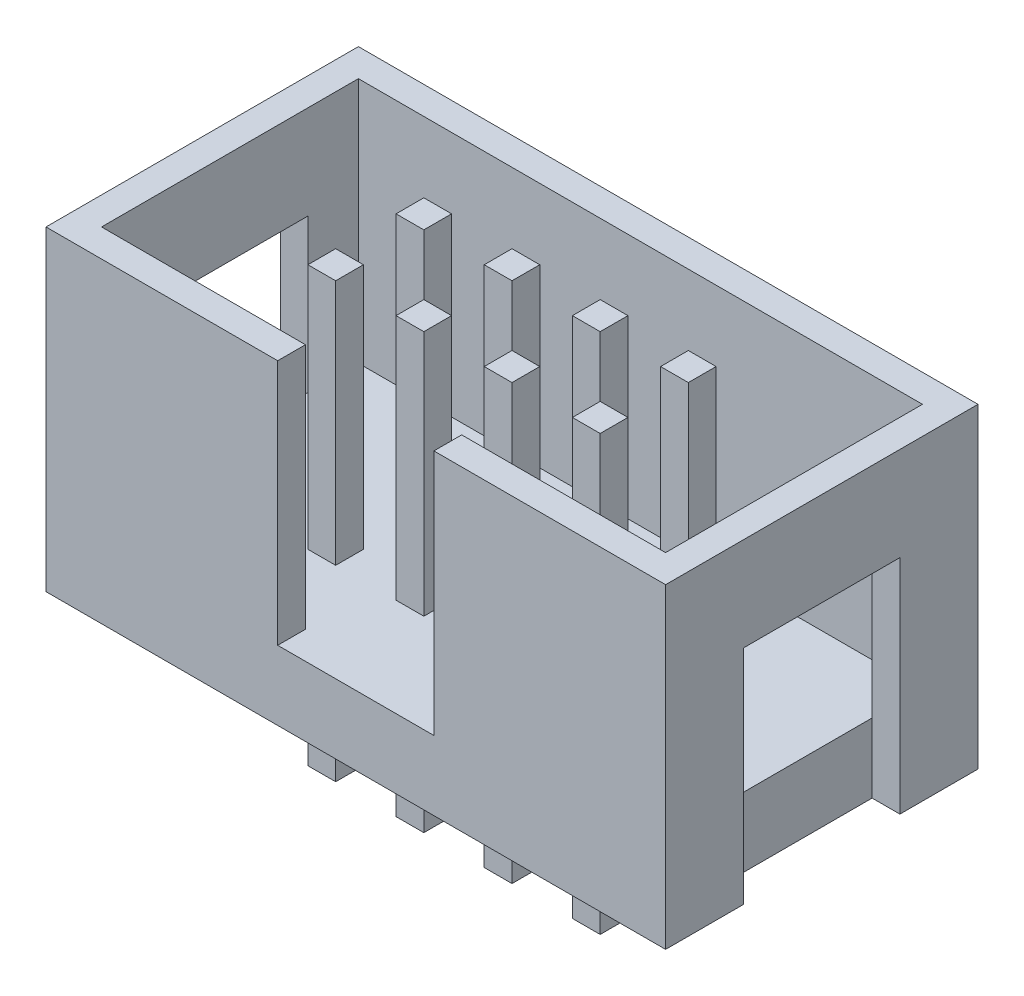
SolidWorks part; units mm, degrees
ref_plane "Front Plane" through (0, 0, 0) normal (0, 0, 1) x (1, 0, 0)
ref_plane "Top Plane" through (0, 0, 0) normal (0, 1, 0) x (1, 0, 0)
ref_plane "Right Plane" through (0, 0, 0) normal (1, 0, 0) x (0, 0, -1)
sketch "Sketch1" plane through (0, 0, 0) normal (0, 1, 0) x (1, 0, 0)
  line L1 (-37.3406, 29.0901) -> (-19.4906, 29.0901)
  line L2 (-37.3406, 29.0901) -> (-37.3406, 20.0901)
  line L3 (-37.3406, 20.0901) -> (-19.4906, 20.0901)
  line L4 (-19.4906, 29.0901) -> (-19.4906, 20.0901)
  dimension "D1" = 9
  dimension "D2" = 17.85
extrude "Boss-Extrude1" add sketch "Sketch1" along normal blind 9.1
sketch "Sketch2" plane through (0, 9.1, 0) normal (0, 1, 0) x (1, 0, 0)
  line L0 (-19.4906, 20.0901) -> (-19.4906, 29.0901) construction
  line L1 (-36.5406, 28.2901) -> (-20.2906, 28.2901)
  line L2 (-36.5406, 28.2901) -> (-36.5406, 20.8901)
  line L3 (-36.5406, 20.8901) -> (-20.2906, 20.8901)
  line L4 (-20.2906, 28.2901) -> (-20.2906, 20.8901)
  line L5 (-37.3406, 20.0901) -> (-19.4906, 20.0901) construction
  line L6 (-37.3406, 29.0901) -> (-37.3406, 20.0901) construction
  line L7 (-19.4906, 29.0901) -> (-37.3406, 29.0901) construction
  line L8 (-37.3406, 25.8601) -> (-19.4906, 25.8601) construction
  line L9 (-37.3406, 23.3201) -> (-19.4906, 23.3201) construction
  line L10 (-37.3406, 24.5901) -> (-19.4906, 24.5901) construction
  line L11 (-29.2856, 23.7201) -> (-29.2856, 22.9201)
  line L12 (-28.4156, 28.2901) -> (-28.4156, 20.8901) construction
  line L17 (-27.5456, 23.7201) -> (-27.5456, 22.9201)
  line L18 (-27.5456, 22.9201) -> (-26.7456, 22.9201)
  line L19 (-26.7456, 23.7201) -> (-26.7456, 22.9201)
  line L20 (-27.5456, 23.7201) -> (-26.7456, 23.7201)
  line L21 (-25.0056, 23.7201) -> (-24.2056, 23.7201)
  line L22 (-25.0056, 23.7201) -> (-25.0056, 22.9201)
  line L23 (-25.0056, 22.9201) -> (-24.2056, 22.9201)
  line L24 (-24.2056, 23.7201) -> (-24.2056, 22.9201)
  line L25 (-29.2856, 23.7201) -> (-30.0856, 23.7201)
  line L32 (-27.5456, 25.4601) -> (-26.7456, 25.4601)
  line L33 (-27.5456, 25.4601) -> (-27.5456, 26.2601)
  line L34 (-27.5456, 26.2601) -> (-26.7456, 26.2601)
  line L35 (-26.7456, 25.4601) -> (-26.7456, 26.2601)
  line L36 (-27.5456, 25.4601) -> (-26.7456, 26.2601) construction
  line L37 (-27.5456, 26.2601) -> (-26.7456, 25.4601) construction
  line L38 (-25.0056, 25.4601) -> (-24.2056, 25.4601)
  line L39 (-25.0056, 25.4601) -> (-25.0056, 26.2601)
  line L40 (-25.0056, 26.2601) -> (-24.2056, 26.2601)
  line L41 (-24.2056, 25.4601) -> (-24.2056, 26.2601)
  line L42 (-25.0056, 25.4601) -> (-24.2056, 26.2601) construction
  line L43 (-25.0056, 26.2601) -> (-24.2056, 25.4601) construction
  line L44 (-30.0856, 23.7201) -> (-30.0856, 22.9201)
  line L45 (-29.2856, 22.9201) -> (-30.0856, 22.9201)
  line L46 (-29.2856, 25.4601) -> (-29.2856, 26.2601)
  line L47 (-29.2856, 26.2601) -> (-30.0856, 26.2601)
  line L48 (-30.0856, 25.4601) -> (-30.0856, 26.2601)
  line L49 (-29.2856, 25.4601) -> (-30.0856, 25.4601)
  line L50 (-31.8256, 23.7201) -> (-31.8256, 22.9201)
  line L51 (-31.8256, 23.7201) -> (-32.6256, 23.7201)
  line L52 (-32.6256, 23.7201) -> (-32.6256, 22.9201)
  line L53 (-31.8256, 22.9201) -> (-32.6256, 22.9201)
  line L54 (-31.8256, 25.4601) -> (-31.8256, 26.2601)
  line L55 (-31.8256, 26.2601) -> (-32.6256, 26.2601)
  line L56 (-32.6256, 25.4601) -> (-32.6256, 26.2601)
  line L57 (-31.8256, 25.4601) -> (-32.6256, 25.4601)
  point P18 (-24.6056, 25.8601)
  point P22 (-27.1456, 25.8601)
  dimension "D7" = 0.8
  dimension "D1" = 0.8
  dimension "D2" = 0.8
  dimension "D3" = 0.8
  dimension "D4" = 0.8
  dimension "D5" = 2.54
  dimension "D6" = 1.27
  dimension "D9" = 2.54
  dimension "D8" = 2.54
extrude "Cut-Extrude1" cut sketch "Sketch2" against normal blind 7.1 contours L3 L4 L1 L2
extrude "Boss-Extrude2" add sketch "Sketch2<3>" against normal blind 12.5 contours L38 L41 L40 L39 | L24 L21 L22 L23 | L20 L17 L18 L19 | L32 L35 L34 L33 | L45 L11 L25 L44 | L49 L46 L47 L48 | L57 L54 L55 L56 | L53 L50 L51 L52
sketch "Sketch2<3>" plane through (0, 9.1, 0) normal (0, 1, 0) x (1, 0, 0) same geometry as "Sketch2"
sketch "Sketch3" plane through (0, 0, -20.0901) normal (0, 0, 1) x (1, 0, 0)
  line L0 (-37.3406, 9.1) -> (-19.4906, 9.1) construction
  line L1 (-30.6656, 9.1) -> (-26.1656, 9.1)
  line L2 (-30.6656, 9.1) -> (-30.6656, 2)
  line L3 (-30.6656, 2) -> (-26.1656, 2)
  line L4 (-26.1656, 9.1) -> (-26.1656, 2)
  line L5 (-28.4156, 0) -> (-28.4156, 9.1) construction
  line L6 (-37.3406, 0) -> (-19.4906, 0) construction
  point P10 (-28.4156, 2)
  dimension "D1" = 7.1
  dimension "D2" = 4.5
extrude "Cut-Extrude2" cut sketch "Sketch3" against normal blind 2.1
sketch "Sketch5" plane through (-37.3406, 0, 0) normal (-1, 0, 0) x (0, 0, 1)
  line L0 (-24.5901, 0) -> (-24.5901, 9.1) construction
  line L1 (-26.8401, 0) -> (-22.3401, 0)
  line L2 (-26.8401, 0) -> (-26.8401, 6.4)
  line L3 (-26.8401, 6.4) -> (-22.3401, 6.4)
  line L4 (-22.3401, 0) -> (-22.3401, 6.4)
  line L7 (-29.0901, 0) -> (-20.0901, 0) construction
  line L8 (-29.0901, 9.1) -> (-20.0901, 9.1) construction
  point P7 (-24.5901, 6.4)
  dimension "D1" = 6.4
  dimension "D2" = 4.5
extrude "Cut-Extrude3" cut sketch "Sketch5" against normal up to surface (0.8 mm away) up to face at (-36.5406, 5.55, -24.5901)
sketch "Sketch6" plane through (-19.4906, 0, 0) normal (1, 0, 0) x (0, 0, -1)
  line L0 (24.5901, 0) -> (24.5901, 9.1) construction
  line L1 (22.3401, 0) -> (26.8401, 0)
  line L2 (22.3401, 0) -> (22.3401, 6.4)
  line L3 (22.3401, 6.4) -> (26.8401, 6.4)
  line L4 (26.8401, 0) -> (26.8401, 6.4)
  line L5 (20.0901, 0) -> (29.0901, 0) construction
  line L6 (20.0901, 9.1) -> (29.0901, 9.1) construction
  point P14 (24.5901, 6.4)
  dimension "D1" = 4.5
  dimension "D2" = 6.4
extrude "Cut-Extrude4" cut sketch "Sketch6" against normal up to surface (0.8 mm away) up to face at (-20.2906, 5.55, -24.5901)
